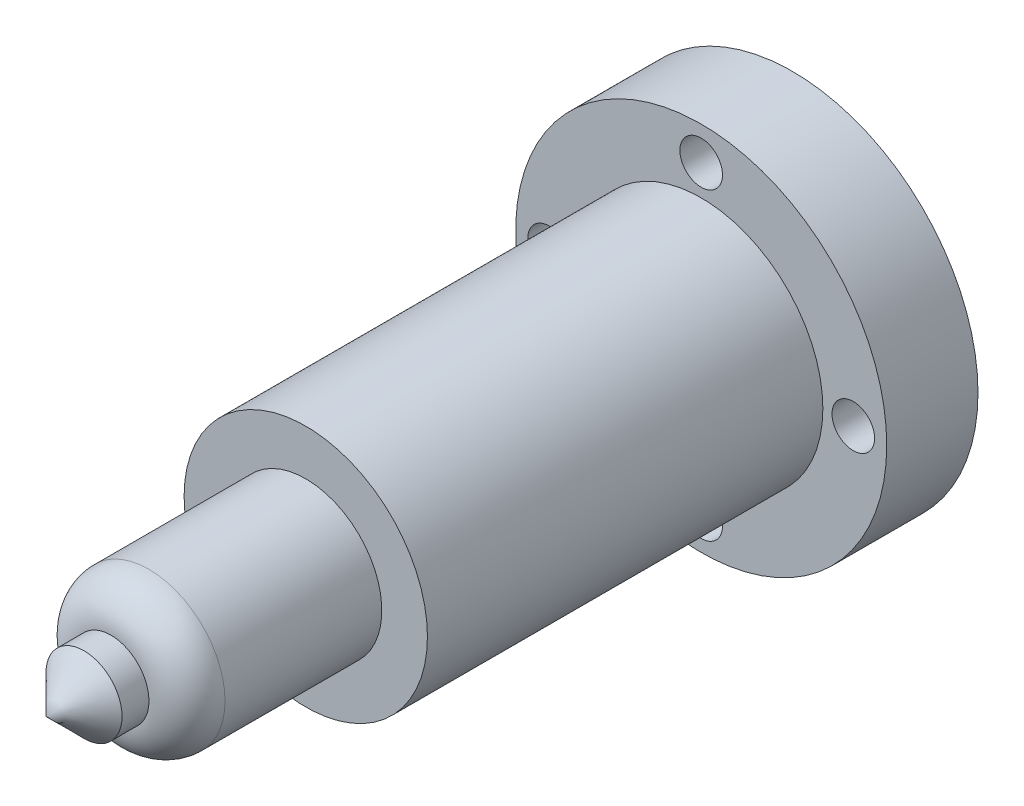
SolidWorks part; units mm, degrees
ref_plane "Front Plane" through (0, 0, 0) normal (0, 0, 1) x (1, 0, 0)
ref_plane "Top Plane" through (0, 0, 0) normal (0, 1, 0) x (1, 0, 0)
ref_plane "Right Plane" through (0, 0, 0) normal (1, 0, 0) x (0, 0, -1)
sketch "Sketch1" plane through (0, 0, 0) normal (0, 0, 1) x (1, 0, 0)
  circle A0 centre (0, 0) radius 30.5
  dimension "D1" = 61
extrude "Boss-Extrude1" add sketch "Sketch1" along normal blind 15
sketch "Sketch2" plane through (0, 0, 15) normal (0, 0, 1) x (1, 0, 0)
  circle A0 centre (0, 0) radius 25 construction
  circle A1 centre (0, 25) radius 3.5
  circle A2 centre (25, 0) radius 3.5
  circle A3 centre (0, -25) radius 3.5
  circle A4 centre (-25, 0) radius 3.5
  point P14 (0, 0)
  dimension "D1" = 50
  dimension "D2" = 7
  dimension "D3" = 4
extrude "Cut-Extrude1" cut sketch "Sketch2" against normal blind 15
sketch "Sketch3" plane through (0, 0, 15) normal (0, 0, 1) x (1, 0, 0)
  circle A0 centre (0, 0) radius 20
  dimension "D1" = 40
extrude "Boss-Extrude2" add sketch "Sketch3" along normal blind 65
sketch "Sketch4" plane through (0, 0, 80) normal (0, 0, 1) x (1, 0, 0)
  circle A0 centre (0, 0) radius 12.5
  dimension "D1" = 25
extrude "Boss-Extrude3" add sketch "Sketch4" along normal blind 42.7
sketch "Sketch5" plane through (0, 0, 122.7) normal (0, 0, 1) x (1, 0, 0)
  circle A0 centre (0, 0) radius 6.25
  circle A1 centre (0, 0) radius 12.5
  circle A2 centre (0, 0) radius 12.5 construction
  dimension "D1" = 12.5
extrude "Cut-Extrude2" cut sketch "Sketch5" against normal blind 10.675
fillet "Fillet1" radius 6.25 1 edges at (12.5, 0, 112.025)
chamfer "Chamfer1" distance 6.25 angle 45 1 edges at (6.25, 0, 122.7)
